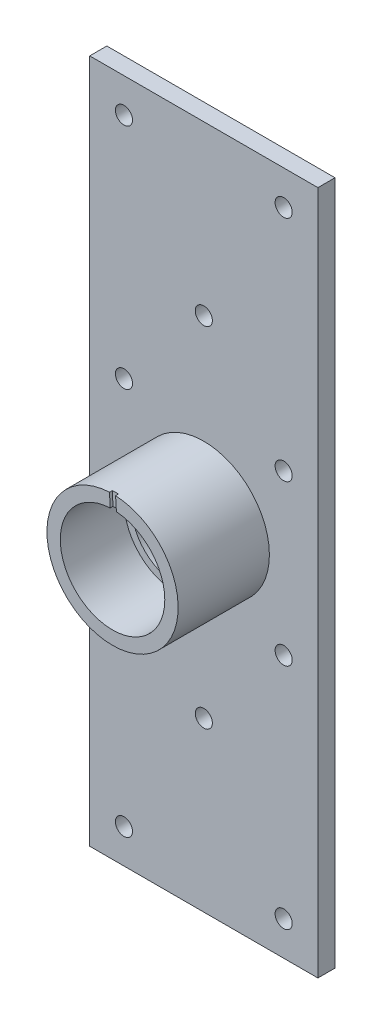
SolidWorks part; units mm, degrees
ref_plane "Front Plane" through (0, 0, 0) normal (0, 0, 1) x (1, 0, 0)
ref_plane "Top Plane" through (0, 0, 0) normal (0, 1, 0) x (1, 0, 0)
ref_plane "Right Plane" through (0, 0, 0) normal (1, 0, 0) x (0, 0, -1)
sketch "Sketch1" plane through (0, 0, 0) normal (0, 0, 1) x (1, 0, 0)
  line L5 (-31.75, 95.25) -> (31.75, 95.25)
  line L6 (-31.75, 95.25) -> (-31.75, -95.25)
  line L7 (-31.75, -95.25) -> (31.75, -95.25)
  line L8 (31.75, 95.25) -> (31.75, -95.25)
  line L9 (-31.75, 95.25) -> (31.75, -95.25) construction
  line L10 (-31.75, -95.25) -> (31.75, 95.25) construction
  point P5 (0, 0)
  dimension "D1" = 63.5
  dimension "D2" = 190.5
extrude "Boss-Extrude1" add sketch "Sketch1" along normal blind 4.7625
sketch "Sketch3" plane through (0, 0, 4.7625) normal (0, 0, 1) x (1, 0, 0)
  circle A0 centre (0, 0) radius 6.35
  dimension "D1" = 12.7
extrude "Cut-Extrude1" cut sketch "Sketch3" against normal blind 0.508
sketch "Sketch4" plane through (0, 0, 4.7625) normal (0, 0, 1) x (1, 0, 0)
  circle A0 centre (0, 0) radius 18.2562
  dimension "D1" = 36.5125
extrude "Boss-Extrude2" add sketch "Sketch4" along normal blind 38.1 contours A0
sketch "Sketch5" plane through (0, 0, 42.8625) normal (0, 0, 1) x (1, 0, 0)
  circle A0 centre (0, 0) radius 12.4619
  dimension "D1" = 24.9237
extrude "Cut-Extrude2" cut sketch "Sketch5" against normal blind 38.1 contours A0
sketch "Sketch7" plane through (0, 0, 42.8625) normal (0, 0, 1) x (1, 0, 0)
  circle A0 centre (0, 0) radius 14.2875
  dimension "D1" = 28.575
extrude "Cut-Extrude3" cut sketch "Sketch7" against normal blind 30.48
hole_wizard "3/16 (0.1875) Diameter Hole1" positions "Sketch8" profile "Sketch9" hole size "3/16" standard "ANSI Inch" end condition through all
sketch "Sketch8" plane through (0, 0, 4.7625) normal (0, 0, 1) x (1, 0, 0)
  line L0 (31.75, 95.25) -> (-31.75, 95.25) construction
  line L1 (31.75, -95.25) -> (31.75, 95.25) construction
  line L2 (-31.75, 95.25) -> (-31.75, -95.25) construction
  line L3 (-31.75, -95.25) -> (31.75, -95.25) construction
  point P0 (-22.225, 85.725)
  point P2 (-22.225, -85.725)
  point P4 (22.225, -85.725)
  point P6 (22.225, 85.725)
  point P17 (0, 48.514)
  point P19 (0, -48.514)
  point P23 (-22.225, 22.225)
  point P26 (-22.225, -22.225)
  point P28 (22.225, -22.225)
  point P30 (22.225, 22.225)
  dimension "D1" = 9.525
  dimension "D2" = 9.525
  dimension "D3" = 9.525
  dimension "D4" = 9.525
  dimension "D5" = 9.525
  dimension "D6" = 9.525
  dimension "D7" = 9.525
  dimension "D8" = 9.525
  dimension "D9" = 48.514
  dimension "D10" = 48.514
  dimension "D11" = 63.5
  dimension "D12" = 63.5
  dimension "D13" = 63.5
  dimension "D14" = 63.5
sketch "Sketch9" plane through (-22.225, 85.725, 4.7625) normal (1, 0, 0) x (0, -1, 0)
  line L0 (0, 0) -> (0, 4.7625)
  line L1 (0, 4.7625) -> (2.3812, 4.7625)
  line L2 (2.3812, 4.7625) -> (2.3812, 0)
  line L5 (2.3812, 0) -> (0, 0)
  line L11 (0, -6.35) -> (0, 107.95) construction
  dimension "Thru Hole Dia." = 4.7625
  dimension "Thru Hole Depth" = 4.7625
sketch "Sketch10" plane through (0, 0, 4.7625) normal (0, 0, 1) x (1, 0, 0)
  line L0 (31.75, 31.75) -> (-31.75, 31.75)
  line L1 (31.75, -95.25) -> (31.75, 95.25) construction
  line L2 (-31.75, 95.25) -> (-31.75, -95.25) construction
  line L3 (31.75, -31.75) -> (-31.75, -31.75)
  point P8 (-31.75, 0)
  dimension "D1" = 31.75
  dimension "D2" = 31.75
sketch "Sketch13" plane through (0, 0, 42.8625) normal (0, 0, 1) x (1, 0, 0)
  circle A0 centre (0, 0) radius 14.5415
  dimension "D1" = 29.083
extrude "Cut-Extrude4" cut sketch "Sketch13" against normal up to surface (30.48 mm away) up to face at (14.2875, 0, 12.3825)
sketch "Sketch14" plane through (0, 0, 42.8625) normal (0, 0, 1) x (1, 0, 0)
  circle A0 centre (0, 0) radius 18.2562
extrude "Cut-Extrude5" cut sketch "Sketch14" against normal blind 12.7
sketch "Sketch15" plane through (0, 0, 30.1625) normal (0, 0, 1) x (1, 0, 0)
  line L0 (0.8404, 18.2369) -> (1.0773, 14.5015)
  line L1 (-0.8423, 18.2368) -> (-0.6709, 14.526)
  circle A0 centre (0, 0) radius 18.2562 construction
  circle A1 centre (0, 0) radius 14.5415 construction
  arc A2 (1.0773, 14.5015) -> (-0.6709, 14.526) centre (-0.0009, -0.0636) ccw
  arc A3 (0.8404, 18.2369) -> (-0.8423, 18.2368) centre (0, 0) ccw
extrude "Cut-Extrude9" cut sketch "Sketch15" against normal blind 0.7937
